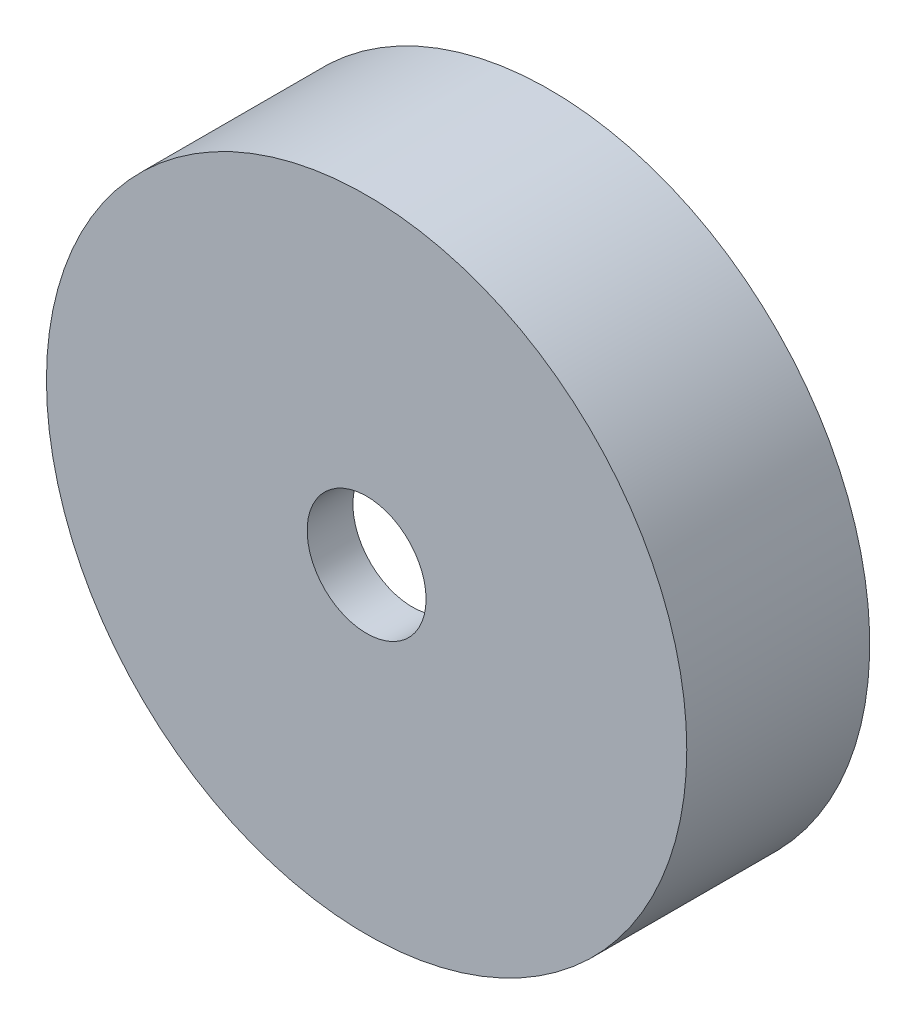
SolidWorks part; units mm, degrees
ref_plane "前视基准面" through (0, 0, 0) normal (0, 0, 1) x (1, 0, 0)
ref_plane "上视基准面" through (0, 0, 0) normal (0, 1, 0) x (1, 0, 0)
ref_plane "右视基准面" through (0, 0, 0) normal (1, 0, 0) x (0, 0, -1)
other "Configuration Table"
sketch "草图2" plane through (0, 0, 0) normal (0, 0, 1) x (1, 0, 0)
  circle A0 centre (0, 0) radius 35
  circle A1 centre (0, 0) radius 6.5
  dimension "D1" = 70
  dimension "D2" = 13
extrude "凸台-拉伸1" add sketch "草图2" along normal blind 5
sketch "草图3" plane through (0, 0, 0) normal (0, 0, -1) x (-1, 0, 0)
  circle A0 centre (0, 0) radius 30
  circle A1 centre (0, 0) radius 35
  dimension "D1" = 60
extrude "凸台-拉伸2" add sketch "草图3" along normal blind 15
sketch "草图4" plane through (0, 0, -15) normal (0, 0, -1) x (-1, 0, 0)
  line L0 (0, 0) -> (0, 32.5)
  line L1 (0, 0) -> (32.5, 0)
  line L2 (0, 0) -> (0, -32.5)
  line L3 (0, 0) -> (-32.5, 0)
  circle A0 centre (0, 32.5) radius 1.55
  circle A1 centre (32.5, 0) radius 1.55
  circle A2 centre (0, -32.5) radius 1.55
  circle A3 centre (-32.5, 0) radius 1.55
  point P9 (0, 0)
  point P17 (0, 0)
  dimension "D2" = 4
  dimension "D1" = 4
extrude "切除-拉伸1" cut sketch "草图4" against normal blind 10 contours A0 | A1 | A2 | A3 region at (1.065, 33.565, -15) region at (-32.5, 1.5062, -15) region at (-1.065, -31.435, -15) region at (34.0062, 0, -15)
sketch "草图9" plane through (0, 0, -15) normal (0, 0, -1) x (-1, 0, 0)
  line L0 (0, 0) -> (0, 32.5) construction
  line L1 (0, 0) -> (-21.2132, 21.2132) construction
  circle A0 centre (0, 0) radius 30 construction
  arc A1 (-21.9426, 20.4579) -> (-20.4579, 21.9426) centre (-21.2132, 21.2132) cw
  arc A2 (20.4579, 21.9426) -> (21.9426, 20.4579) centre (21.2132, 21.2132) cw
  arc A3 (21.9426, -20.4579) -> (20.4579, -21.9426) centre (21.2132, -21.2132) cw
  arc A4 (-20.4579, -21.9426) -> (-21.9426, -20.4579) centre (-21.2132, -21.2132) cw
  arc A5 (-20.4579, 21.9426) -> (-21.9426, 20.4579) centre (0, 0) ccw
  arc A6 (-21.9426, -20.4579) -> (-20.4579, -21.9426) centre (0, 0) ccw
  arc A7 (20.4579, -21.9426) -> (21.9426, -20.4579) centre (0, 0) ccw
  arc A8 (21.9426, 20.4579) -> (20.4579, 21.9426) centre (0, 0) ccw
  point P21 (0, 0)
  dimension "D2" = 1.05
  dimension "D1" = 45
  dimension "D3" = 4
extrude "切除-拉伸5" cut sketch "草图9" against normal up to surface (15 mm away) up to face at (6.5, 0, 0)
fillet "圆角1" radius 1 4 edges at (0, -30, -15) (-30, 0, -15) (0, 30, -15) (30, 0, -15)
sketch "草图10" plane through (0, 0, 0) normal (0, 0, -1) x (-1, 0, 0)
  circle A0 centre (0, 0) radius 29.3
  circle A1 centre (0, 0) radius 30
extrude "凸台-拉伸3" add sketch "草图10" along normal blind 3
